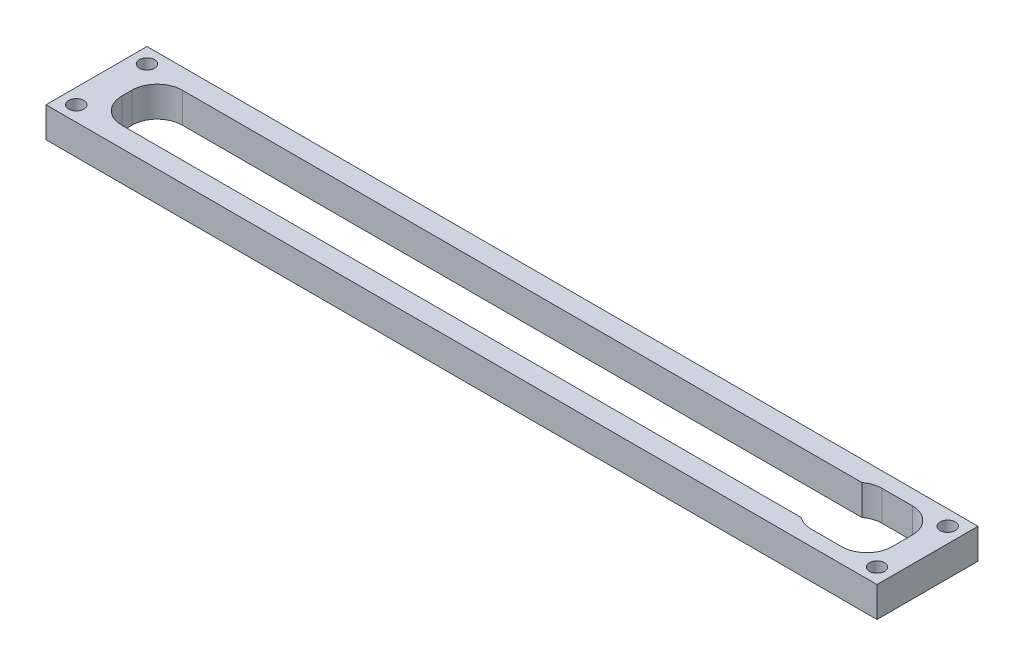
SolidWorks part; units mm, degrees
ref_plane "Front Plane" through (0, 0, 0) normal (0, 0, 1) x (1, 0, 0)
ref_plane "Top Plane" through (0, 0, 0) normal (0, 1, 0) x (1, 0, 0)
ref_plane "Right Plane" through (0, 0, 0) normal (1, 0, 0) x (0, 0, -1)
sketch "Sketch1" plane through (0, 0, 0) normal (0, 1, 0) x (1, 0, 0)
  line L0 (82.2674, 20) -> (82.2674, 0) construction
  line L1 (0, 0) -> (164.5348, 0)
  line L2 (0, 0) -> (0, 20)
  line L3 (0, 20) -> (164.5348, 20)
  line L4 (164.5348, 0) -> (164.5348, 20)
  line L5 (0, 10) -> (164.5348, 10) construction
  line L6 (82.2674, 16) -> (82.2674, 4) construction
  line L7 (6, 16) -> (158.5348, 16)
  line L8 (6, 16) -> (6, 4)
  line L9 (6, 4) -> (158.5348, 4)
  line L10 (158.5348, 16) -> (158.5348, 4)
  line L11 (6, 10) -> (158.5348, 10) construction
  circle A0 centre (3, 17) radius 1.5
  circle A1 centre (3, 3) radius 1.5
  circle A2 centre (161.5348, 3) radius 1.5
  circle A3 centre (161.5348, 17) radius 1.5
  point P17 (82.2674, 10)
  point P18 (82.2674, 10)
  dimension "D7" = 3
  dimension "D1" = 164.5348
  dimension "D2" = 20
  dimension "D3" = 152.5348
  dimension "D4" = 12
  dimension "D5" = 3
  dimension "D6" = 3
extrude "Boss-Extrude1" add sketch "Sketch1" along normal blind 6
sketch "Sketch2" plane through (0, 6, 0) normal (0, 1, 0) x (1, 0, 0)
  line L0 (92, 10) -> (-49908, 10) construction
  line L1 (158.5348, 4) -> (158.5348, 16) construction
  line L2 (145.5348, 17) -> (145.5348, 16)
  line L5 (158.5348, 16) -> (6, 16) construction
  line L6 (152.5348, 17) -> (152.5348, 3) construction
  line L7 (145.5348, 17) -> (159.5348, 17)
  line L9 (145.5348, 3) -> (159.5348, 3)
  line L10 (159.5348, 17) -> (159.5348, 3)
  line L12 (145.5348, 16) -> (158.5348, 16)
  line L13 (158.5348, 16) -> (158.5348, 4)
  line L14 (158.5348, 4) -> (145.5348, 4)
  line L15 (6, 4) -> (158.5348, 4) construction
  line L16 (145.5348, 4) -> (145.5348, 3)
  point P4 (158.5348, 10)
  point P23 (152.5348, 10)
  dimension "D1" = 1
  dimension "D2" = 14
  dimension "D3" = 14
extrude "Cut-Extrude1" cut sketch "Sketch2" against normal through all
fillet "Fillet1" radius 5 6 edges at (159.5348, 3, -17) (159.5348, 3, -3) (145.5348, 3, -17) (145.5348, 3, -3) (6, 3, -4) (6, 3, -16)
equation "\"TrackLength\"= ( ( \"n\" * 28 ) ) / cos ( \"MountAngle\" ) - ( 2 * \"x\" )"
equation "\"D1@Sketch1\"=\"TrackLength\""
equation "\"TrackWidth\"= \"MarbleTrackWidth\" + ( 2 * 4 )"
equation "\"D2@Sketch1\"=\"TrackWidth\""
equation "\"MarbleTrackWidth\"= \"MarbleWidth\" - 1"
equation "\"MarbleTrackLength\"= \"TrackLength\" - ( 2 * 6 )"
equation "\"D3@Sketch1\"=\"MarbleTrackLength\""
equation "\"D4@Sketch1\"=\"MarbleTrackWidth\""
equation "\"MarbleWidth\"= 13"
equation "\"n\"= 6"
equation "\"MountAngle\"= 5"
equation "\"x\"= 14 / cos ( \"MountAngle\" ) - 12"
